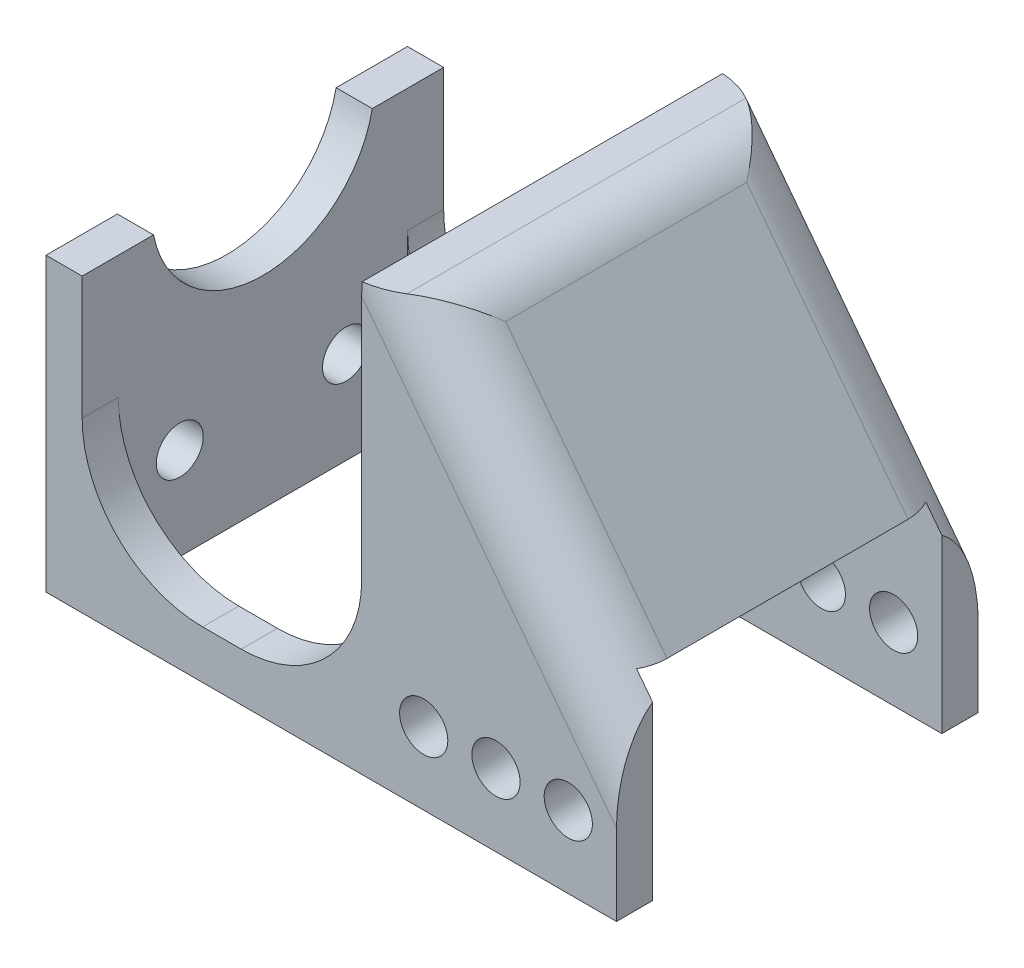
SolidWorks part; units mm, degrees
ref_plane "Front Plane" through (0, 0, 0) normal (0, 0, 1) x (1, 0, 0)
ref_plane "Top Plane" through (0, 0, 0) normal (0, 1, 0) x (1, 0, 0)
ref_plane "Right Plane" through (0, 0, 0) normal (1, 0, 0) x (0, 0, -1)
sketch "Sketch1" plane through (0, 0, 0) normal (0, 0, 1) x (1, 0, 0)
  line L0 (0, 0) -> (-10, -13.0323) construction
  line L1 (0, 0) -> (10, -13.0323) construction
  line L2 (-10, -13.0323) -> (10, -13.0323)
  line L9 (-11.1437, 22.3593) -> (-5.7608, 22.5296)
  line L10 (-11.1437, -9.0323) -> (-11.1437, 22.3593)
  line L11 (10, 1.9125) -> (10, -13.0323)
  line L12 (-5.7608, 22.5296) -> (10, 1.9125)
  line L13 (-10, -13.0323) -> (-37.3437, -13.0323)
  line L14 (-37.3437, -13.0323) -> (-37.3437, 11.1805)
  line L15 (-37.3437, 11.1805) -> (-34.3437, 11.1805)
  line L16 (-34.3437, 11.1805) -> (-34.3437, -9.0323)
  line L17 (-11.1437, -9.0323) -> (-34.3437, -9.0323)
  circle A2 centre (0, -7.0323) radius 2
  circle A3 centre (6, -7.0323) radius 2
  circle A4 centre (-6, -7.0323) radius 2
  dimension "D6" = 4
  dimension "D7" = 4
  dimension "D10" = 4
  dimension "D1" = 75
  dimension "D2" = 20
  dimension "D3" = 35.41
  dimension "D4" = 23.2
  dimension "D5" = 6
  dimension "D8" = 6
  dimension "D9" = 6
  dimension "D11" = 3
  dimension "D12" = 4
extrude "Boss-Extrude1" add sketch "Sketch1" along normal blind 30
sketch "Sketch2" plane through (10, 0, 0) normal (1, 0, 0) x (0, 0, -1)
  line L1 (-27, -13.0323) -> (-3, -13.0323)
  line L2 (-27, -13.0323) -> (-27, 2.9677)
  line L3 (-27, 2.9677) -> (-3, 2.9677)
  line L4 (-3, -13.0323) -> (-3, 2.9677)
  line L5 (-30, -13.0323) -> (0, -13.0323) construction
  dimension "D1" = 16
extrude "Cut-Extrude1" cut sketch "Sketch2" against normal up to surface (44.3437 mm away) up to face at (-34.3437, 1.0741, 15)
sketch "Sketch3" plane through (-11.1437, 0, 0) normal (-1, 0, 0) x (0, 0, 1)
  line L0 (3, 2.9677) -> (27, 2.9677) construction
  circle A0 centre (15, 12.9677) radius 9
  circle A1 centre (15, 12.9677) radius 6 construction
  circle A2 centre (15, 18.9677) radius 2
  circle A3 centre (15, 6.9677) radius 2
  circle A4 centre (9, 12.9677) radius 2
  circle A5 centre (21, 12.9677) radius 2
  point P5 (15, 2.9677)
  dimension "D1" = 18
  dimension "D2" = 10
  dimension "D3" = 12
  dimension "D4" = 4
  dimension "D5" = 4
  dimension "D6" = 4
  dimension "D7" = 4
extrude "Cut-Extrude2" cut sketch "Sketch3" against normal blind 3
fillet "Fillet1" [suppressed] radius 2
sketch "Sketch4" plane through (-34.3437, 0, 0) normal (1, 0, 0) x (0, 0, -1)
  circle A0 centre (-15, 12.9677) radius 2 construction
  arc A1 (-16.9663, 12.6021) -> (-13.0337, 13.3334) centre (-15, 12.9677) ccw construction
  arc A2 (-16.9663, 12.6021) -> (-13.0337, 13.3334) centre (-15, 12.9677) ccw construction
  circle A3 centre (-15, 12.9677) radius 9.25
  dimension "D1" = 4
  dimension "D2" = 18.5
extrude "Cut-Extrude3" cut sketch "Sketch4" against normal through all
fillet "Fillet2" radius 10 4 edges at (-11.1437, -9.0323, 1.5) (-11.1437, -9.0323, 28.5) (-34.3437, -9.0323, 28.5) (-34.3437, -9.0323, 1.5)
fillet "Fillet3" radius 5 3 edges at (-5.7608, 22.5296, 15) (2.1196, 12.2211, 30) (2.1196, 12.2211, 0)
hole_wizard "M3.5 Clearance Hole1" positions "Sketch5" profile "Sketch6" hole size "M3.5" standard "ANSI Metric" end condition through all
sketch "Sketch5" plane through (-37.3437, 0, 0) normal (-1, 0, 0) x (0, 0, 1)
  point P0 (8.1, -5.3723)
  point P3 (21.9, -5.3723)
sketch "Sketch6" plane through (-37.3437, -5.3723, 8.1) normal (0, 1, 0) x (0, 0, 1)
  line L0 (0, 0) -> (0, 47.3437)
  line L1 (0, 47.3437) -> (1.95, 47.3437)
  line L2 (1.95, 47.3437) -> (1.95, 0.025)
  line L3 (1.95, 0.025) -> (1.975, 0)
  line L5 (1.975, 0) -> (0, 0)
  line L6 (-1.95, 0.025) -> (-1.975, 0) construction
  line L11 (0, -6.35) -> (0, 107.95) construction
  dimension "Thru Hole Dia." = 3.9
  dimension "Thru Hole Depth" = 47.3437
  dimension "Near C'Sink Dia." = 3.95
  dimension "Near C'Sink Angle" = 90
